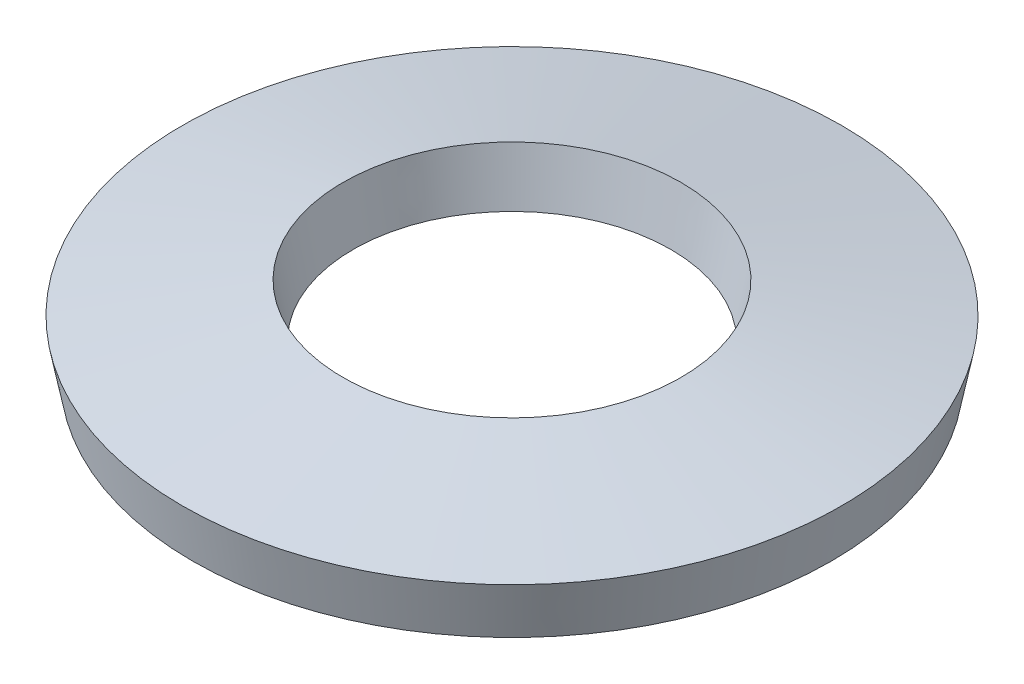
SolidWorks part; units mm, degrees
ref_plane "Front" through (0, 0, 0) normal (0, 0, 1) x (1, 0, 0)
ref_plane "Top" through (0, 0, 0) normal (0, 1, 0) x (1, 0, 0)
ref_plane "Right" through (0, 0, 0) normal (1, 0, 0) x (0, 0, -1)
sketch "Sketch1" plane through (0, 0, 0) normal (0, 0, 1) x (1, 0, 0)
  line L0 (5.3297, 0) -> (2.65, 0.5163)
  line L1 (2.65, 0.5163) -> (2.8203, 1.4)
  line L2 (2.8203, 1.4) -> (5.5, 0.8837)
  line L3 (5.5, 0.8837) -> (5.3297, 0)
  line L4 (0, 0) -> (0, 1.4) construction
  line L5 (-5.5, 0.8837) -> (-5.3297, 0) construction
  line L6 (-2.8203, 1.4) -> (-5.5, 0.8837) construction
  line L7 (-2.65, 0.5163) -> (-2.8203, 1.4) construction
  line L8 (-5.3297, 0) -> (-2.65, 0.5163) construction
  point P5 (2.7351, 0.9581)
  point P8 (-2.7351, 0.9581)
  dimension "D1" = 2.729
  dimension "ID" = 5.3
  dimension "OD" = 11
  dimension "Thickness" = 0.9
  dimension "Height" = 1.4
revolve "Revolve1" add sketch "Sketch1" angle 360 about L4
sketch "Sketch15" plane through (0, 0, 0) normal (0, 1, 0) x (1, 0, 0)
  circle A0 centre (0, 0) radius 5.5
  circle A1 centre (0, 0) radius 2.65
ref_plane "Contact Plane 1" through (0, 0, 0) normal (0, 1, 0) x (-1, 0, 0)
ref_plane "Contact Plane 2" through (0, 1.4, 0) normal (0, 1, 0) x (-1, 0, 0)
ref_axis "Center Axis 1" through (0, 0, 0) along (0, 1, 0)
ref_axis "Axis1" through (0, 1.4, 0) along (0, -1, 0)
